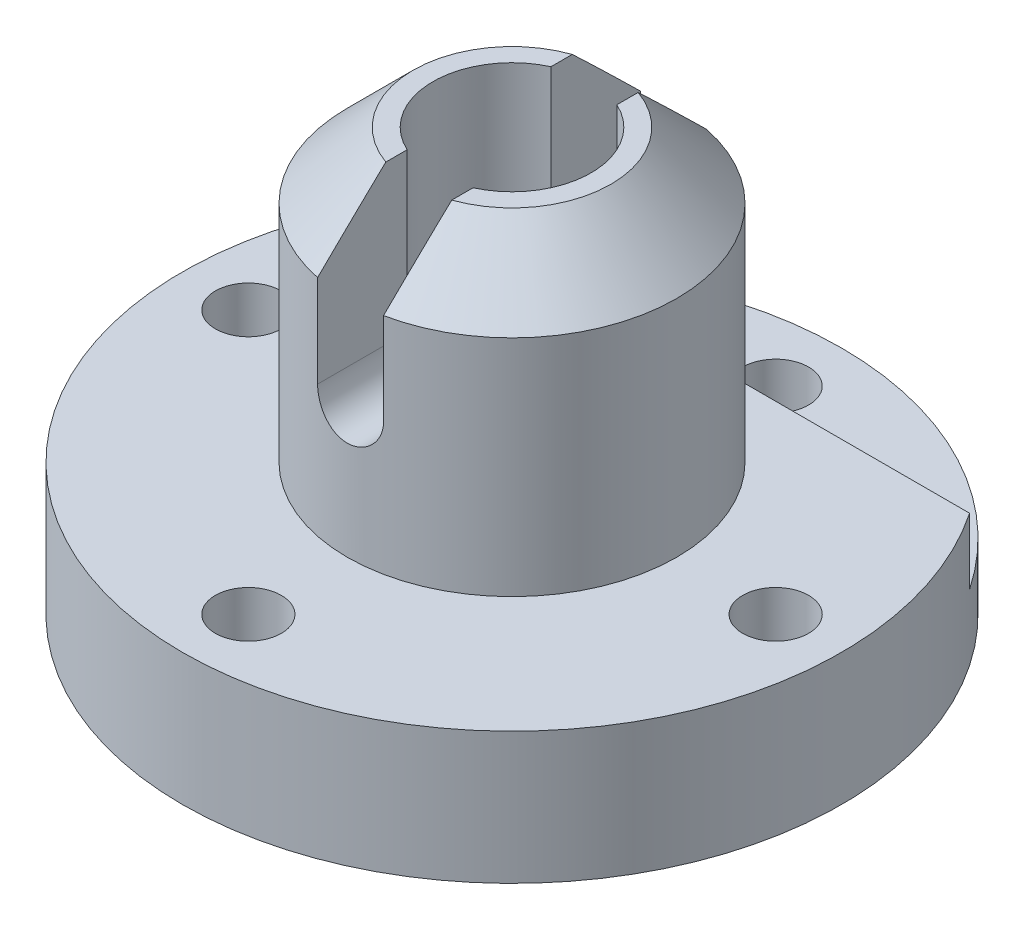
SolidWorks part; units mm, degrees
ref_plane "Front Plane" through (0, 0, 0) normal (0, 0, 1) x (1, 0, 0)
ref_plane "Top Plane" through (0, 0, 0) normal (0, 1, 0) x (1, 0, 0)
ref_plane "Right Plane" through (0, 0, 0) normal (1, 0, 0) x (0, 0, -1)
sketch "Sketch1" plane through (0, 0, 0) normal (0, 1, 0) x (1, 0, 0)
  line L0 (-20.7123, 14) -> (20.7123, 14)
  circle A0 centre (0, 0) radius 25
  circle A1 centre (0, 0) radius 12.5
  circle A2 centre (0, 0) radius 6
  dimension "D1" = 50
  dimension "D2" = 25
  dimension "D3" = 12
  dimension "D4" = 14
extrude "Boss-Extrude1" add sketch "Sketch1" along normal blind 10 contours A0
extrude "Boss-Extrude2" add sketch "Sketch1<3>" along normal blind 32 contours A1 A2 region at (-12.1464, 0, 0)
sketch "Sketch1<3>" plane through (0, 0, 0) normal (0, 1, 0) x (1, 0, 0) same geometry as "Sketch1"
extrude "Cut-Extrude1" cut sketch "Sketch1<5>" along normal up to surface (10 mm away) from offset 5 contours L0 A0 region at (0, 0, -18.4952) up to face at (0, 10, 12.5)
sketch "Sketch1<5>" plane through (0, 0, 0) normal (0, 1, 0) x (1, 0, 0) same geometry as "Sketch1"
sketch "Sketch2" plane through (0, 0, 0) normal (0, 0, 1) x (1, 0, 0)
  line L0 (0, 32) -> (0, 0) construction
  line L1 (12.5, 32) -> (-12.5, 32) construction
  line L3 (-2.5, 20) -> (2.5, 20)
  line L4 (-2.5, 20) -> (-2.5, 32)
  line L5 (-2.5, 32) -> (2.5, 32)
  line L6 (2.5, 20) -> (2.5, 32)
  circle A0 centre (0, 20) radius 2.5
  dimension "D1" = 5
  dimension "D2" = 12
extrude "Cut-Extrude2" cut sketch "Sketch2" against normal through all both and the other way through all contours L0 L5 L4 A0 | L5 L0 A0 L6 | A0 L0 L3 | L0 L3 A0 | L0 A0 L3 | L3 L0 A0 region at (1.287, 26.9662, 0) region at (-1.287, 26.9662, 0) region at (1.061, 21.061, 0) region at (-1.061, 21.061, 0) region at (1.061, 18.939, 0) region at (-1.061, 18.939, 0)
sketch "Sketch3" plane through (0, 0, 0) normal (0, 1, 0) x (1, 0, 0)
  line L0 (0, 0) -> (0, 28.2461) construction
  circle A0 centre (0, 20) radius 2.5
  dimension "D2" = 5
  dimension "D1" = 20
extrude "Cut-Extrude3" cut sketch "Sketch3" along normal through all contours A0
pattern_circular "CirPattern1" count 4 over 360 about axis through (0, 10, 0) along (0, 1, 0) of "Cut-Extrude3"
chamfer "Chamfer1" distance 5 angle 45 2 edges at (-12.5, 32, 0) (12.5, 32, 0)
